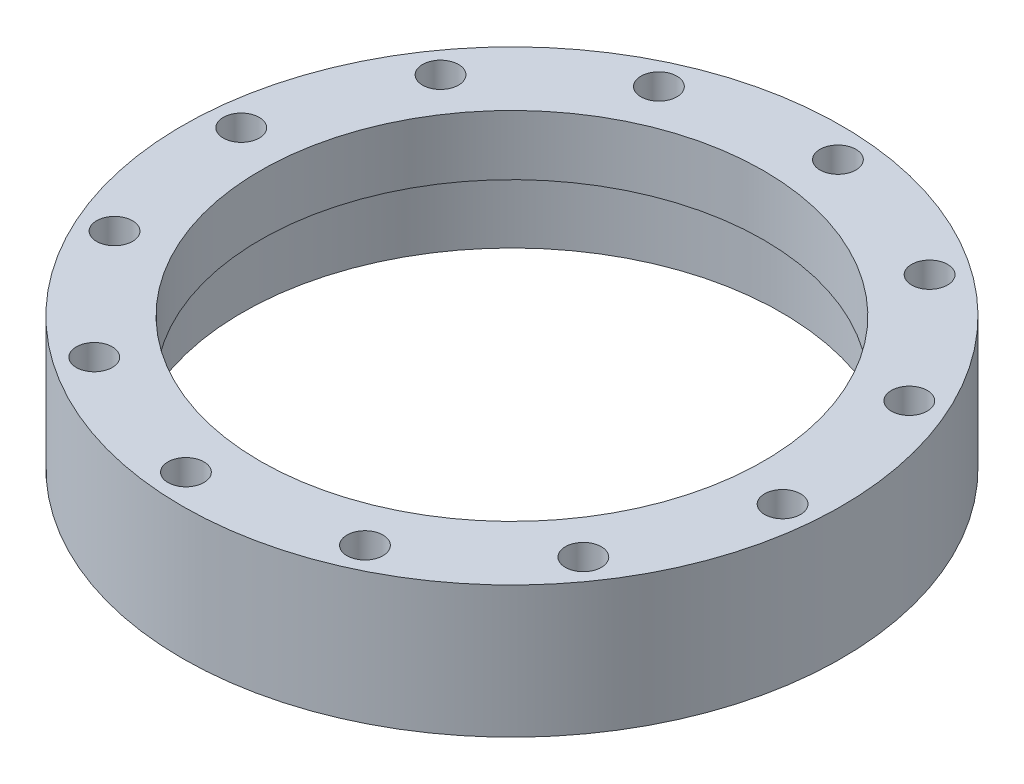
SolidWorks part; units mm, degrees
ref_plane "Front Plane" through (0, 0, 0) normal (0, 0, 1) x (1, 0, 0)
ref_plane "Top Plane" through (0, 0, 0) normal (0, 1, 0) x (1, 0, 0)
ref_plane "Right Plane" through (0, 0, 0) normal (1, 0, 0) x (0, 0, -1)
sketch "Sketch1" plane through (0, 0, 0) normal (0, 1, 0) x (1, 0, 0)
  circle A0 centre (0, 0) radius 27.5
  circle A1 centre (0, 0) radius 25 construction
  circle A2 centre (0, 0) radius 22.5
  circle A3 centre (2.3086, 24.8932) radius 1.5
  circle A4 centre (14.4459, 20.4038) radius 1.5
  circle A5 centre (22.7124, 10.4472) radius 1.5
  circle A6 centre (24.8932, -2.3086) radius 1.5
  circle A7 centre (20.4038, -14.4459) radius 1.5
  circle A8 centre (10.4472, -22.7124) radius 1.5
  circle A9 centre (-2.3086, -24.8932) radius 1.5
  circle A10 centre (-14.4459, -20.4038) radius 1.5
  circle A11 centre (-22.7124, -10.4472) radius 1.5
  circle A12 centre (-24.8932, 2.3086) radius 1.5
  circle A13 centre (-20.4038, 14.4459) radius 1.5
  circle A14 centre (-10.4472, 22.7124) radius 1.5
  point P31 (0, 0)
  dimension "D1" = 55
  dimension "D2" = 50
  dimension "D3" = 45
  dimension "D4" = 3
  dimension "D5" = 12
extrude "Boss-Extrude1" add sketch "Sketch1" along normal blind 11
sketch "Sketch2" plane through (0, 11, 0) normal (0, 1, 0) x (1, 0, 0)
  circle A0 centre (0, 0) radius 22.5
  circle A1 centre (0, 0) radius 21
  dimension "D1" = 42
extrude "Boss-Extrude2" add sketch "Sketch2" against normal blind 5
